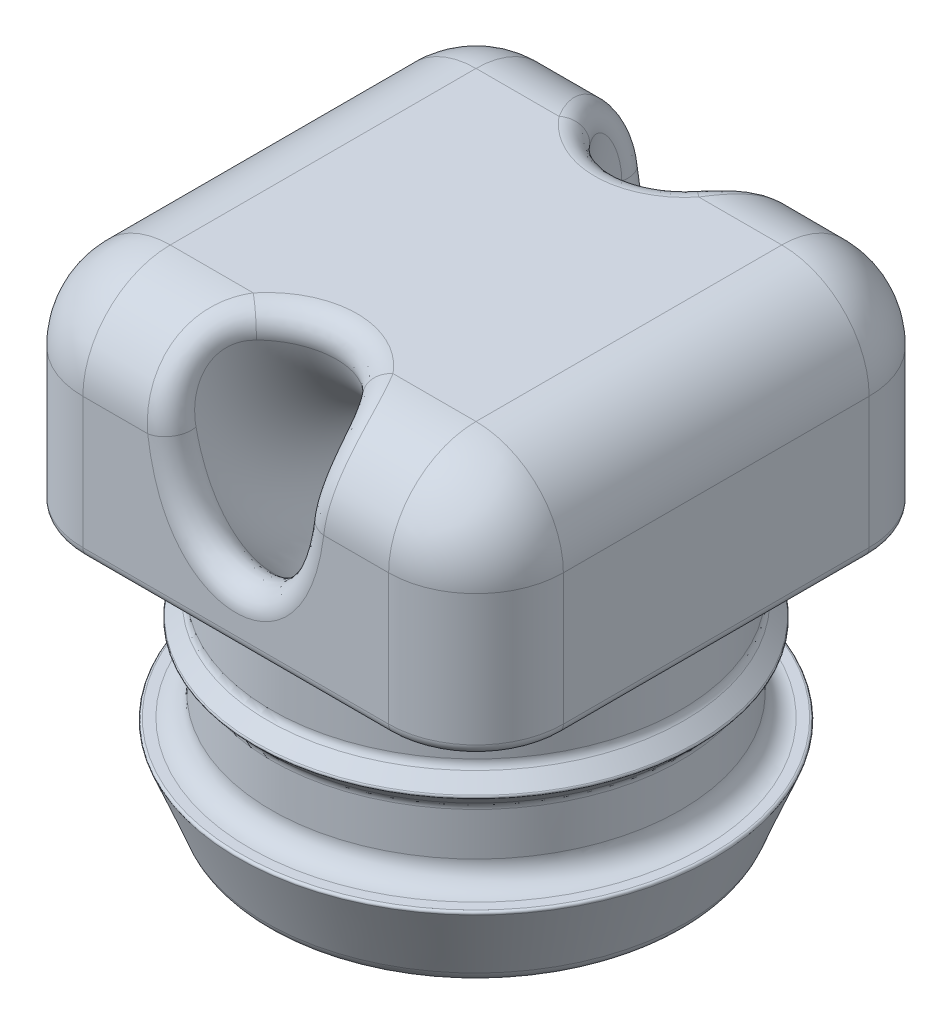
SolidWorks part; units mm, degrees
ref_plane "Front Plane" through (0, 0, 0) normal (0, 0, 1) x (1, 0, 0)
ref_plane "Top Plane" through (0, 0, 0) normal (0, 1, 0) x (1, 0, 0)
ref_plane "Right Plane" through (0, 0, 0) normal (1, 0, 0) x (0, 0, -1)
sketch "Sketch1" plane through (0, 0, 0) normal (0, 0, 1) x (1, 0, 0)
  line L3 (0, 0) -> (0, -10.5) construction
  line L5 (-11, 0) -> (-11, -10.5)
  line L6 (-11, -10.5) -> (11, -10.5)
  line L7 (11, 0) -> (11, -10.5)
  line L16 (-11, 0) -> (11, 0)
  point P1 (11, -10.5)
  point P4 (0, 0)
  dimension "D1" = 10.5
  dimension "D4" = 22
extrude "Upper-Body" add sketch "Sketch1" along normal mid plane 22
sketch3d "3DSketch1" plane through (0, 0, 0) normal (0, 0, 1) x (1, 0, 0)
  dimension "D1" = 12.7
sketch "Sketch2" plane through (0, 0, 0) normal (0, 0, 1) x (1, 0, 0)
  line L0 (0, 9.544) -> (0, -9.544) construction
  line L1 (0, -10) -> (9.365, -10)
  line L4 (0, -22.7) -> (9.365, -22.7)
  line L10 (0, -22.7) -> (0, -10)
  line L11 (9.365, -22.7) -> (10.9525, -18.7312)
  line L12 (10.9525, -18.7312) -> (9.365, -18.7312)
  line L13 (9.365, -18.7312) -> (9.365, -15.5562)
  line L14 (9.365, -15.5562) -> (10.1587, -14.7625)
  line L15 (10.1587, -14.7625) -> (9.365, -13.9687)
  line L16 (10.1587, -14.7625) -> (9.365, -14.7625) construction
  line L17 (9.365, -13.9687) -> (9.365, -10)
  dimension "D1" = 18.73
  dimension "D2" = 12.7
  dimension "D3" = 1.5875
  dimension "D4" = 3.9688
  dimension "D5" = 0.7937
  dimension "D6" = 7.9375
  dimension "D7" = 10
revolve "Barb" add sketch "Sketch2" angle 360 about L0
sketch "Sketch6" plane through (0, 0, 0) normal (1, 0, 0) x (0, 0, -1)
  line L1 (0, 1) -> (0, 0) construction
  line L2 (-11, 0) -> (11, 0) construction
  circle A0 centre (0, 1) radius 10
  dimension "D1" = 20
  dimension "D2" = 1
sweep "Tendon-Loop" cut path "Sketch6" circular profile diameter 6.4 parameters "D3"=6.4
fillet "Fillet-4-0" radius 4 10 edges at (-11, 0, 0) (11, 0, 0) (-11, -5.25, 11) (-11, -5.25, -11) (11, -5.25, 11) (11, -5.25, -11) (-7.0122, 0, -11) (7.0122, 0, -11) (7.0122, 0, 11) (-7.0122, 0, 11)
fillet "Fillet-1.0" radius 1 11 edges at (-0.1325, 8.2916, 11) (-0.1325, 8.2916, -11) (-3.121, -0.6268, 9.1498) (-0.4711, 0, 6.7613) (3.1722, -0.8056, 9.4074) (3.121, -0.6268, -9.1498) (0.5722, 0, -6.7782) (-3.1722, -0.8056, -9.4074) (-9.365, -10.5, 0) (-9.365, -22.7, 0) (-9.365, -18.7312, 0)
fillet "Fillet-0.5" radius 0.5 10 edges at (-11, -10.5, 0) (0, -10.5, -11) (11, -10.5, 0) (0, -10.5, 11) (-9.8284, -10.5, 9.8284) (-9.8284, -10.5, -9.8284) (9.8284, -10.5, -9.8284) (9.8284, -10.5, 9.8284) (-9.365, -15.5562, 0) (-9.365, -13.9688, 0)
fillet "Fillet1" radius 0.1 2 edges at (-10.1587, -14.7625, 0) (-10.9525, -18.7312, 0)
